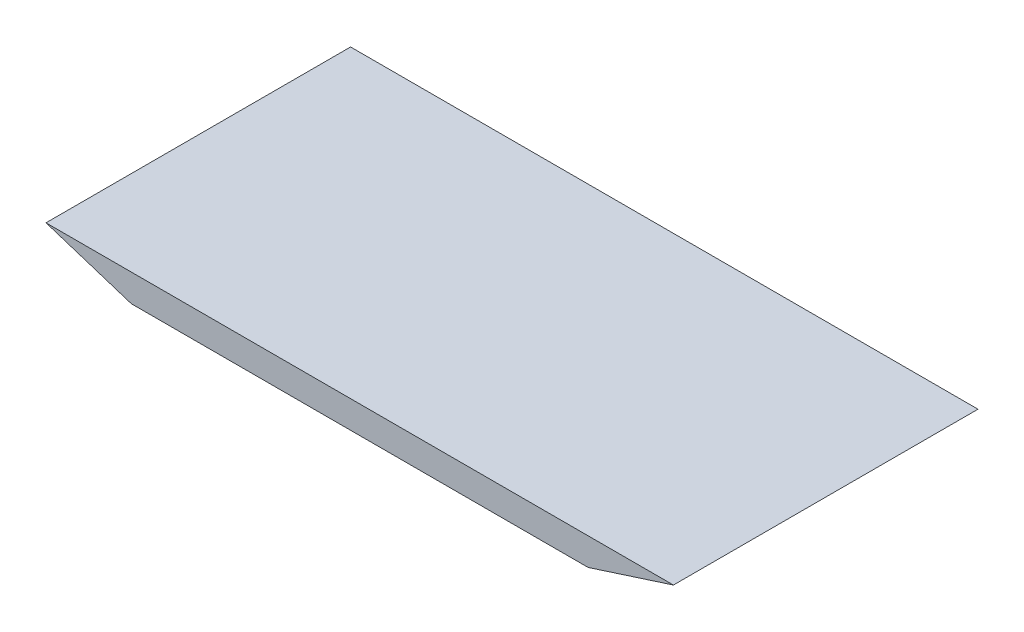
SolidWorks part; units mm, degrees
ref_plane "Front Plane" through (0, 0, 0) normal (0, 0, 1) x (1, 0, 0)
ref_plane "Top Plane" through (0, 0, 0) normal (0, 1, 0) x (1, 0, 0)
ref_plane "Right Plane" through (0, 0, 0) normal (1, 0, 0) x (0, 0, -1)
sketch "Sketch1" plane through (0, 0, 0) normal (0, 0, 1) x (1, 0, 0)
  line L0 (0, 0) -> (206, 0)
  line L1 (206, 0) -> (178, -9)
  line L2 (178, -9) -> (28, -9)
  line L3 (28, -9) -> (0, 0)
  point P7 (186.6381, -9.9066)
  dimension "D1" = 150
  dimension "D2" = 9
  dimension "D3" = 28
  dimension "D4" = 28
extrude "Boss-Extrude1" add sketch "Sketch1" along normal blind 100
